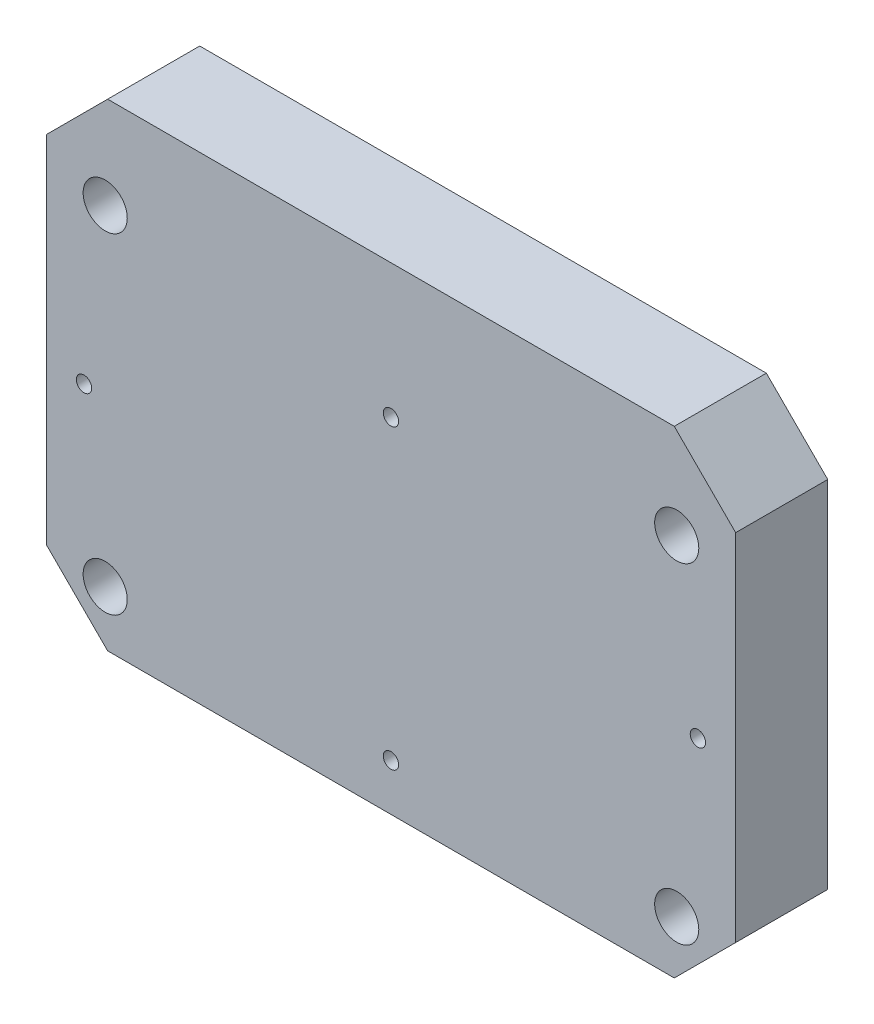
SolidWorks part; units mm, degrees
material "Beech"
ref_plane "Front Plane" through (0, 0, 0) normal (0, 0, 1) x (1, 0, 0)
ref_plane "Top Plane" through (0, 0, 0) normal (0, 1, 0) x (1, 0, 0)
ref_plane "Right Plane" through (0, 0, 0) normal (1, 0, 0) x (0, 0, -1)
sketch "Sketch1" plane through (0, 0, 0) normal (0, 0, 1) x (1, 0, 0)
  line L0 (165.475, 390.3924) -> (-165.475, 390.3924) construction
  line L1 (71.3145, 489.2361) -> (-71.3145, 489.2361)
  line L2 (71.3145, 489.2361) -> (71.3145, 390.3924)
  line L3 (71.3145, 390.3924) -> (-71.3145, 390.3924)
  line L4 (-71.3145, 489.2361) -> (-71.3145, 390.3924)
  line L5 (71.3145, 489.2361) -> (-71.3145, 489.2361) construction
  line L6 (-71.3145, 489.2361) -> (-71.3145, 470.1861) construction
  point P4 (-60.6575, 487.0896)
  point P5 (71.3145, 489.2361)
  point P7 (71.3145, 390.3924)
  point P10 (-71.3145, 489.2361)
  point P13 (-71.3145, 489.2361)
extrude "Boss-Extrude1" add sketch "Sketch1" along normal blind 19.05
chamfer "Chamfer1" distance 12.7 angle 45 4 edges at (-71.3145, 390.3924, 9.525) (-71.3145, 489.2361, 9.525) (71.3145, 390.3924, 9.525) (71.3145, 489.2361, 9.525)
hole_wizard "23/64 (0.35938) Diameter Hole1" positions "Sketch2" profile "Sketch4" hole size "23/64" standard "ANSI Inch" end condition through all
sketch "Sketch2" plane through (0, 0, 19.05) normal (0, 0, 1) x (1, 0, 0)
  point P0 (-59.12, 469.9425)
  point P3 (59.12, 469.9425)
  point P6 (59.12, 401.6165)
  point P9 (-59.12, 401.6165)
sketch "Sketch4" plane through (-59.12, 469.9425, 19.05) normal (1, 0, 0) x (0, -1, 0)
  line L0 (0, 0) -> (0, 19.05)
  line L1 (0, 19.05) -> (4.5641, 19.05)
  line L2 (4.5641, 19.05) -> (4.5641, 0)
  line L5 (4.5641, 0) -> (0, 0)
  line L11 (0, -6.35) -> (0, 107.95) construction
  dimension "Thru Hole Dia." = 9.1283
  dimension "Thru Hole Depth" = 19.05
hole_wizard "Hole1" positions "Sketch5" profile "Sketch6" legacy
sketch "Sketch5" plane through (0, 0, -19.05) normal (0, 0, -1) x (-1, 0, 0)
  line L0 (0, 470.1861) -> (0, 390.3924) construction
  line L4 (0, 435.7795) -> (-63.5, 435.7795) construction
  point P9 (-63.5, 435.7795)
  point P12 (0, 461.5584)
  point P14 (0, 400.0751)
  point P20 (0, 0)
  point P21 (63.5, 435.7795)
sketch "Sketch6" plane through (-63.5, 435.7795, -19.05) normal (1, 0, 0) x (0, 1, 0)
  line L0 (0, 0) -> (0, 45.4039)
  line L1 (0, 45.4039) -> (1.5875, 44.45)
  line L2 (1.5875, 44.45) -> (1.5875, 4.0177)
  line L3 (1.5875, 4.0177) -> (5.08, 0)
  line L4 (5.08, 0) -> (0, 0)
  line L5 (0, -14.3089) -> (0, 102.4216) construction
  line L6 (0, 45.4039) -> (-1.5875, 44.45) construction
  line L7 (-1.5875, 4.0177) -> (-5.08, 0) construction
  dimension "Diameter" = 3.175
  dimension "Depth" = 44.45
  dimension "C-Sink Diameter" = 10.16
  dimension "C-Sink Angle" = 82
  dimension "Drill Angle" = 118
